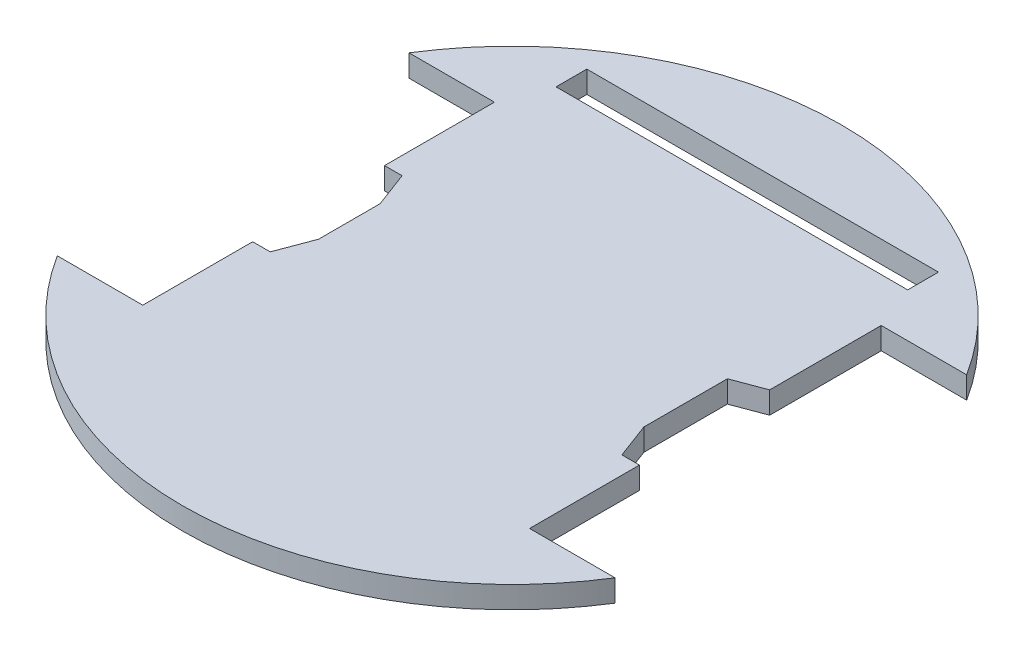
SolidWorks part; units mm, degrees
ref_plane "Front Plane" through (0, 0, 0) normal (0, 0, 1) x (1, 0, 0)
ref_plane "Top Plane" through (0, 0, 0) normal (0, 1, 0) x (1, 0, 0)
ref_plane "Right Plane" through (0, 0, 0) normal (1, 0, 0) x (0, 0, -1)
sketch "Sketch1" plane through (0, 0, 0) normal (0, 1, 0) x (1, 0, 0)
  line L0 (0, 86.8325) -> (0, -90.8838) construction
  line L1 (86.1573, 0) -> (-106.4137, 0) construction
  line L5 (-44, -40) -> (-44, -15)
  line L16 (-44, -15) -> (-37, -15)
  line L17 (40, 50.0244) -> (-40, 50.0244)
  line L18 (40, 50.0244) -> (40, 57.0244)
  line L19 (40, 57.0244) -> (-40, 57.0244)
  line L20 (-40, 50.0244) -> (-40, 57.0244)
  line L21 (40, 50.0244) -> (-40, 57.0244) construction
  line L22 (40, 57.0244) -> (-40, 50.0244) construction
  line L32 (-44, -40) -> (-63.4429, -40)
  line L33 (-37, -15) -> (-37, 15)
  line L34 (-44, 40) -> (-63.4429, 40)
  line L35 (-44, 15) -> (-37, 15)
  line L36 (-44, 40) -> (-44, 15)
  line L37 (44, 40) -> (44, 15)
  line L38 (44, 15) -> (37, 15)
  line L39 (44, 40) -> (63.4429, 40)
  line L40 (37, -15) -> (37, 15)
  line L41 (44, -40) -> (63.4429, -40)
  line L42 (44, -15) -> (37, -15)
  line L43 (44, -40) -> (44, -15)
  arc A0 (-63.4429, -40) -> (63.4429, -40) centre (0, 0) ccw
  arc A1 (63.4429, 40) -> (-63.4429, 40) centre (0, 0) ccw
  point P1 (0, 53.5244)
  point P9 (-75, 0)
  point P10 (-37, 0)
  point P13 (75, 0)
  point P14 (-44.5598, 0)
  dimension "D2" = 150
  dimension "D1" = 38
  dimension "D3" = 31
  dimension "D5" = 80
  dimension "D6" = 7
extrude "Boss-Extrude1" add sketch "Sketch1" along normal blind 5
chamfer "Chamfer1" distance 3 distance2 8 4 edges at (37, 2.5, 15) (37, 2.5, -15) (-37, 2.5, 15) (-37, 2.5, -15) first distance on face at (40.5, 2.5, 15) first distance on face at (37, 2.5, 0) first distance on face at (-40.5, 2.5, 15) first distance on face at (-40.5, 2.5, -15)
